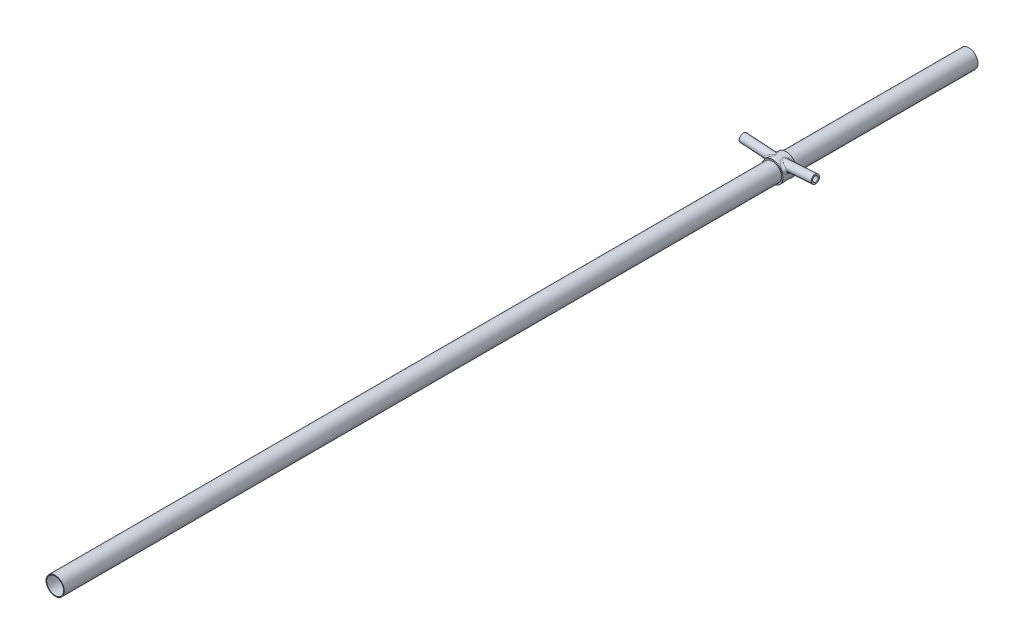
SolidWorks part; units mm, degrees
material "6061-T6 (SS)"
ref_plane "Front Plane" through (0, 0, 0) normal (0, 0, 1) x (1, 0, 0)
ref_plane "Top Plane" through (0, 0, 0) normal (0, 1, 0) x (1, 0, 0)
ref_plane "Right Plane" through (0, 0, 0) normal (1, 0, 0) x (0, 0, -1)
sketch "Sketch1" plane through (0, 0, 0) normal (0, 0, 1) x (1, 0, 0)
  circle A0 centre (0, 0) radius 20
  circle A1 centre (0, 0) radius 23
  dimension "D1" = 40
  dimension "D2" = 3
extrude "Boss-Extrude1" add sketch "Sketch1" along normal blind 30
ref_axis "Axis1" through (0, 0, 30) along (0, 0, -1)
ref_plane "Plane1" through (0, 0, 0) normal (0.9976, 0.0698, 0) x (0, 0, -1)
sketch "Sketch2" plane through (0, 0, 0) normal (0.9976, 0.0698, 0) x (0, 0, -1)
  line L0 (-15, 12.3446) -> (-15, 0) construction
  line L1 (-30, 0) -> (0, 0) construction
  line L2 (-30, 12.3446) -> (0, 12.3446) construction
  line L3 (-30, 23) -> (-30, -23) construction
  line L4 (0, -23) -> (0, 23) construction
  circle A0 centre (-15, 12.3446) radius 9
  circle A1 centre (-15, 12.3446) radius 7
  dimension "D1" = 18
  dimension "D2" = 2
extrude "Boss-Extrude2" add sketch "Sketch2" against normal up to next from offset 80 contours A0 A1 | A1 region at (-0.8611, 12.3145, 23.7454) region at (-0.8611, 12.3145, 15)
sketch "Sketch4" plane through (79.8051, 5.5805, 0) normal (0.9976, 0.0698, 0) x (0, 0, -1)
  circle A0 centre (-15, 12.3446) radius 5.8
  circle A1 centre (-15, 12.3446) radius 9 construction
  dimension "D1" = 3.2
extrude "Cut-Extrude2" cut sketch "Sketch4" against normal blind 50
mirror "Mirror1" about plane through (0, 0, 0) normal (1, 0, 0) of "Boss-Extrude2"
fillet "Fillet1" radius 5 2 edges at (-7.1086, 21.8739, 14.4031) (22.3351, 5.4904, 11.8361)
sketch "Sketch3" plane through (0, 0, 0) normal (0, 1, 0) x (1, 0, 0)
  line L0 (-8, -15) -> (8, -15) construction
  line L1 (-8, -3) -> (8, -3)
  line L2 (-8, -27) -> (8, -27)
  line L4 (-20, -30) -> (20, -30) construction
  line L5 (0, -30) -> (0, 0) construction
  arc A0 (-8, -3) -> (-8, -27) centre (-8, -15) ccw
  arc A1 (8, -27) -> (8, -3) centre (8, -15) ccw
  point P2 (0, -15)
  dimension "D1" = 3
  dimension "D2" = 3
  dimension "D3" = 16
extrude "Cut-Extrude1" cut sketch "Sketch3" against normal through all
ref_plane "Plane2" through (0, 0, -400) normal (0, 0, -1) x (-1, 0, 0)
sketch "Sketch6" plane through (0, 0, -400) normal (0, 0, -1) x (-1, 0, 0)
  circle A0 centre (0, 0) radius 20 construction
  circle A1 centre (0, 0) radius 20
  circle A2 centre (0, 0) radius 18.5
  dimension "D1" = 1.5
extrude "Boss-Extrude3" add sketch "Sketch6" against normal blind 2000 separate body
sketch "Sketch7" plane through (0, 0, 0) normal (1, 0, 0) x (0, 0, -1)
  line L0 (-1600, -20) -> (400, -20)
  line L1 (400, 20) -> (-1600, 20)
  line L2 (400, 20) -> (-1600, 20) construction
  line L3 (-1600, -20) -> (390.8176, -20) construction
  line L4 (483.2707, 23.2) -> (-1600, 23.2) construction
  line L5 (289.5, 23.2) -> (483.2707, 23.2) construction
  line L6 (483.2707, 23.2) -> (561.9968, 23.2) construction
  line L7 (561.9968, 23.2) -> (785.4224, -5.5717) construction
  line L8 (785.4224, -5.5717) -> (901.0533, -143.267) construction
  line L9 (901.0533, -143.267) -> (1003.0096, -224.3769) construction
  line L10 (1003.0096, -224.3769) -> (871.1608, -237.2812) construction
  line L11 (871.1608, -237.2812) -> (828.2651, -340.5369) construction
  line L12 (828.2651, -340.5369) -> (784.6295, -169.0285) construction
  line L13 (506.7989, -177.5494) -> (462.2208, -242.7531) construction
  line L14 (462.2208, -242.7531) -> (418.8934, -323.7696) construction
  line L15 (418.8934, -323.7696) -> (369.2679, -186.2126) construction
  line L16 (369.2679, -186.2126) -> (328.9729, -104.7483) construction
  line L17 (328.9729, -104.7483) -> (289.5, -23.2) construction
  line L18 (289.5, 23.2) -> (289.5, -23.2) construction
  line L19 (-1600, -23.2) -> (390.288, -23.2) construction
  line L20 (400, 23.2) -> (-1600, 23.2) construction
  line L21 (-1600, -23.2) -> (390.8176, -23.2) construction
  line L22 (400, 20) -> (850, 20) construction
  line L23 (400, 20) -> (400, -230) construction
  line L24 (400, -230) -> (850, -230) construction
  line L25 (850, 20) -> (850, -230) construction
  line L26 (784.6295, -169.0285) -> (506.7989, -177.5494) construction
  spline_without_curve S0
  point P18 (389.1029, -23.1706)
  point P21 (360.1996, -39.7599)
  point P22 (0, 0)
  point P24 (0, 0)
  point P27 (392.0318, -67.4482)
  point P28 (0, 0)
  point P29 (385.4902, -82.9729)
  point P30 (0, 0)
  point P32 (378.5563, -114.2289)
  point P33 (346.5192, -68.3912)
  point P37 (414.5364, -153.1664)
  point P38 (348.3634, -68.8294)
  point P39 (336.2313, -80.8603)
  point P40 (413.4626, -170.5482)
  point P41 (344.2036, -75.3793)
  point P44 (508.8103, -152.1028)
  point P45 (784.2616, -158.5899)
  point P46 (827.0858, -342.2691)
  point P47 (462.2546, -240.2945)
  point P48 (375.4797, -126.6555)
  point P49 (418.8965, -323.9424)
  point P51 (340.4858, -101.0997)
  point P52 (289.5003, -23.2)
  point P53 (328.9729, -104.8003)
  point P54 (369.2679, -186.2126)
  dimension "D3" = 450
  dimension "D4" = 250
  dimension "D1" = 3.2
  dimension "D2" = 3.2
sketch "Sketch8" plane through (0, 0, 0) normal (1, 0, 0) x (0, 0, -1)
  line L0 (850, -181.7678) -> (223.1723, -181.7678) construction
  line L1 (850, 20) -> (850, -230) construction
  spline S0 degree 14 poles (289.5, 23.2) (483.2707, 23.2) (561.9968, 23.2) (785.4224, -5.5717) (901.0533, -143.267) (1003.0096, -224.3769) (871.1608, -237.2812) (828.2651, -340.5369) (784.6295, -169.0285) (506.7989, -177.5494) (462.2208, -242.7531) (418.8934, -323.7696) (369.2679, -186.2126) (328.9729, -104.7483) (289.5, -23.2) knots 0 0 0 0 0 0 0 0 0 0 0 0 0 0 0 1 1 1 1 1 1 1 1 1 1 1 1 1 1 1 construction
  point P4 (0, 0)
  point P5 (449.8366, -181.7678)
  point P6 (0, 0)
  point P7 (223.1723, -181.7678)
  point P8 (317.9974, -23.2)
  point P10 (0, 0)
  point P11 (317.9974, -23.2)
  point P12 (317.9974, -23.2)
  point P13 (533.3855, -181.4705)
  point P14 (0, 0)
  point P16 (0, 0)
  point P17 (317.9974, 23.2)
  point P18 (850, -181.4705)
  point P19 (0, 0)
  point P20 (317.9974, -23.2)
  point P22 (0, 0)
ref_plane "Plane3" through (0, 0, -289.5) normal (0, 0, 1) x (1, 0, 0)
sketch "Sketch9" plane through (0, 0, -289.5) normal (0, 0, 1) x (1, 0, 0)
  arc A0 (0, 23.2) -> (0, -23.2) centre (0, 0) cw
  point P5 (5.3292, -22.5796)
ref_plane "Plane4" through (0, -181.7678, 0) normal (0, 1, 0) x (1, 0, 0)
sketch "Sketch10" plane through (0, -181.7678, 0) normal (0, 1, 0) x (1, 0, 0)
  line L2 (0, 850) -> (69.7256, 850) construction
  line L4 (69.7256, 850) -> (74.6721, 697.058) construction
  line L5 (74.6721, 697.058) -> (57.6155, 571.336) construction
  line L8 (57.6155, 571.336) -> (0, 379.3331) construction
  line L10 (0, 850) -> (60, 850) construction
  line L11 (0, 850) -> (0, 379.3331) construction
  line L12 (0, 379.3331) -> (60, 379.3331) construction
  line L13 (60, 850) -> (60, 379.3331) construction
  spline S0 degree 4 poles (0, 850) (69.7256, 850) (74.6721, 697.058) (57.6155, 571.336) (0, 379.3331) knots 0 0 0 0 0 1 1 1 1 1
  point P1 (86.7953, 697.1247)
  point P2 (68.6035, 850)
  point P3 (57.6155, 571.336)
  point P7 (0, 0)
  dimension "D1" = 60
ref_plane "Plane5" through (0, -235.6339, -235.6339) normal (0, 0.7071, 0.7071) x (1, 0, 0)
ref_plane "Plane6" through (0, -285.1314, -285.1314) normal (0, 0.7071, 0.7071) x (1, 0, 0)
